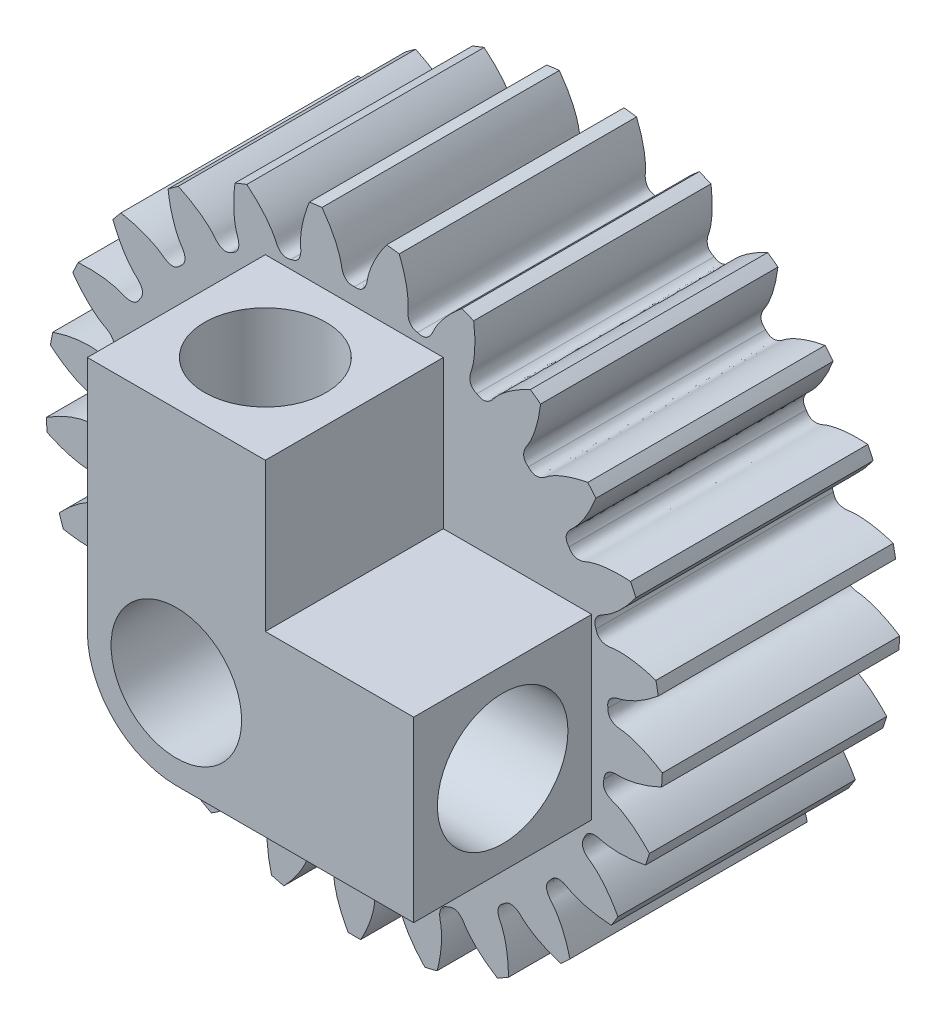
SolidWorks part; units mm, degrees
material "PLA Black"
ref_plane "Front" through (0, 0, 0) normal (0, 0, 1) x (1, 0, 0)
ref_plane "Top" through (0, 0, 0) normal (0, 1, 0) x (1, 0, 0)
ref_plane "Right" through (0, 0, 0) normal (1, 0, 0) x (0, 0, -1)
ref_axis "Axis1" through (0, 0, -80.9) along (0, 0, 1)
sketch "Gear-BaseSketch" plane through (0, 0, 0) normal (0, 0, 1) x (1, 0, 0)
  circle A0 centre (0, 0) radius 10.3909
  dimension "D1" = 20.7818
extrude "33.0 Diametral Pitch, 20.78mm P.D." add sketch "Gear-BaseSketch" along normal mid plane 8
sketch "Tooth-Sketch; Backlash: 0.0000mm" plane through (0, 0, 0) normal (0, 0, 1) x (1, 0, 0)
  line L0 (0, 0) -> (0, 10.3909) construction
  arc A0 (-1.0905, 10.334) -> (1.0905, 10.334) centre (0, -0.094) cw
  circle A1 centre (0, 0) radius 10.3909 construction
  spline S0 degree 3 poles (-1.0905, 10.334) (-1.0138, 10.2299) (-0.9082, 10.0753) (-0.7851, 9.8689) (-0.7088, 9.729) (-0.6442, 9.5985) (-0.5903, 9.4783) (-0.5464, 9.369) (-0.5115, 9.2711) (-0.4845, 9.1851) (-0.4645, 9.1115) (-0.4506, 9.0507) (-0.4416, 9.0039) (-0.4365, 8.9698) (-0.432, 8.9444) (-0.4246, 8.9083) (-0.4122, 8.8596) (-0.3912, 8.7995) (-0.3638, 8.742) (-0.3272, 8.686) (-0.2761, 8.6321) (-0.1724, 8.5642) (-0.0681, 8.5594) (0, 8.5647) knots 0 0 0 0 0.176711 0.2556 0.328177 0.394444 0.454399 0.508044 0.555377 0.596399 0.63111 0.65951 0.681599 0.696189 0.706616 0.716848 0.746535 0.775185 0.80367 0.83335 0.866218 0.904587 1 1 1 1
  spline S1 degree 3 poles (1.0905, 10.334) (1.0138, 10.2299) (0.9082, 10.0753) (0.7851, 9.8689) (0.7088, 9.729) (0.6442, 9.5985) (0.5903, 9.4783) (0.5464, 9.369) (0.5115, 9.2711) (0.4845, 9.1851) (0.4645, 9.1115) (0.4506, 9.0507) (0.4416, 9.0039) (0.4365, 8.9698) (0.432, 8.9444) (0.4246, 8.9083) (0.4122, 8.8596) (0.3912, 8.7995) (0.3638, 8.742) (0.3272, 8.686) (0.2761, 8.6321) (0.1724, 8.5642) (0.0681, 8.5594) (0, 8.5647) knots 0 0 0 0 0.176711 0.2556 0.328177 0.394444 0.454399 0.508044 0.555377 0.596399 0.63111 0.65951 0.681599 0.696189 0.706616 0.716848 0.746535 0.775185 0.80367 0.83335 0.866218 0.904587 1 1 1 1
extrude "Tooth-Cut, Fine Pitch Involute 20 deg" cut sketch "Tooth-Sketch; Backlash: 0.0000mm" against normal through all and the other way through all
pattern_circular "Tooth Pattern, 25 / 25" count 25 over 360 about axis through (0, 0, -80.9) along (0, 0, 1) of "Tooth-Cut, Fine Pitch Involute 20 deg"
sketch "Sketch4" plane through (0, 0, 4) normal (0, 0, 1) x (1, 0, 0)
  circle A0 centre (0, 0) radius 2.2
  dimension "D1" = 4.4
extrude "Cut-Extrude2" cut sketch "Sketch4" against normal through all contours A0
sketch "Sketch6" plane through (0, 0, 4) normal (0, 0, 1) x (1, 0, 0)
  circle A0 centre (0, 0) radius 3
  circle A1 centre (0, 0) radius 2.2
  circle A2 centre (0, 0) radius 2.2 construction
  dimension "D1" = 6
extrude "Boss-Extrude2" add sketch "Sketch6" along normal blind 6
sketch "Sketch9" plane through (0, 0, 4) normal (0, 0, 1) x (1, 0, 0)
  line L0 (-3, 0) -> (-3, 8)
  line L1 (-3, 8) -> (3, 8)
  line L2 (3, 8) -> (3, 3)
  line L3 (3, 3) -> (8, 3)
  line L4 (8, 3) -> (8, -3)
  line L5 (8, -3) -> (0, -3)
  circle A0 centre (0, 0) radius 3 construction
  circle A1 centre (0, 0) radius 3 construction
  arc A2 (-3, 0) -> (0, -3) centre (0, 0) cw
  dimension "D1" = 5
extrude "Boss-Extrude4" add sketch "Sketch9" along normal through all
ref_plane "Plane1" through (0, 3, 0) normal (0, 1, 0) x (1, 0, 0)
sketch "Sketch10" plane through (0, 8, 0) normal (0, 1, 0) x (1, 0, 0)
  line L0 (-3, -7) -> (3, -7) construction
  line L1 (-3, -10) -> (-3, -4) construction
  line L2 (3, -10) -> (3, -4) construction
  line L3 (0, -4) -> (0, -10) construction
  line L4 (3, -10) -> (-3, -10) construction
  circle A0 centre (0, -7) radius 2.05
  dimension "D1" = 4.1
extrude "Cut-Extrude3" cut sketch "Sketch10" against normal blind 8
sketch "Sketch11" plane through (8, 0, 0) normal (1, 0, 0) x (0, 0, -1)
  line L0 (-7, 3) -> (-7, -3) construction
  line L1 (-10, 3) -> (-4, 3) construction
  line L2 (-10, -3) -> (-4, -3) construction
  line L3 (-10, 0) -> (-4, 0) construction
  line L4 (-10, -3) -> (-10, 3) construction
  line L7 (-4, -3) -> (-4, 3) construction
  circle A0 centre (-7, 0) radius 2.2
  dimension "D1" = 4.4
extrude "Cut-Extrude4" cut sketch "Sketch11" against normal blind 8 contours A0
